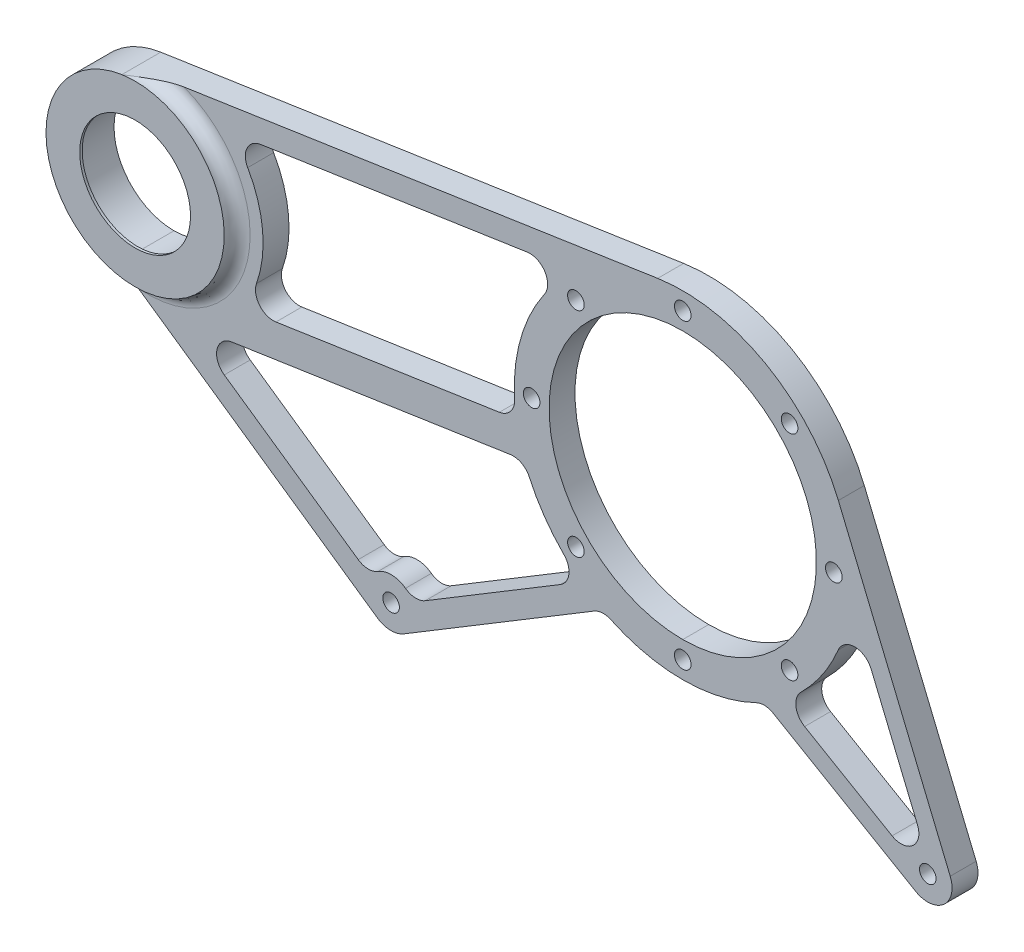
SolidWorks part; units mm, degrees
material "6061-T6 (SS)"
ref_plane "Front Plane" through (0, 0, 0) normal (0, 0, 1) x (1, 0, 0)
ref_plane "Top Plane" through (0, 0, 0) normal (0, 1, 0) x (1, 0, 0)
ref_plane "Right Plane" through (0, 0, 0) normal (1, 0, 0) x (0, 0, -1)
sketch "Sketch1" plane through (0, 0, 0) normal (0, 0, 1) x (1, 0, 0)
  line L0 (-329.0358, 136.1378) -> (-124.1059, 166.9079)
  line L1 (-343.7594, 72.9056) -> (-234.0298, -3.2296)
  line L2 (-223.6766, -3.5577) -> (-149.0272, 41.5159)
  line L3 (-114.3, 88.9) -> (-114.3, 101.6) construction
  line L4 (-53.3056, 126.9173) -> (-9.4675, 21.3025)
  line L5 (-23.0618, 9.4221) -> (-78.8665, 41.9532)
  circle A0 centre (-114.3, 88.9) radius 82.9716 construction
  circle A1 centre (-228.6, -20.8038) radius 12.7 construction
  circle A2 centre (0, 0) radius 12.7 construction
  circle A3 centre (-323.85, 101.6) radius 114 construction
  circle A4 centre (-323.85, 101.6) radius 23.5
  circle A5 centre (-114.3, 101.6) radius 52.3875
  arc A6 (-142.4404, 41.8555) -> (-85.4371, 42.2012) centre (-114.3, 101.6) ccw
  circle A7 centre (-323.85, 101.6) radius 34.925
  arc A8 (-223.6766, -3.5577) -> (-234.0298, -3.2296) centre (-228.6, 4.5962) cw
  arc A9 (-9.4675, 21.3025) -> (-23.0618, 9.4221) centre (-18.2648, 17.651) cw
  circle A10 centre (-228.6, 4.5962) radius 3.2512
  circle A11 centre (-18.2648, 17.651) radius 3.2512
  arc A12 (-142.4404, 41.8555) -> (-149.0272, 41.5159) centre (-145.4168, 35.5364) ccw
  arc A13 (-78.8665, 41.9532) -> (-85.4371, 42.2012) centre (-82.3843, 35.9187) ccw
  circle A14 centre (-114.3, 101.6) radius 66.04 construction
  arc A15 (-124.1059, 166.9079) -> (-53.3056, 126.9173) centre (-114.3, 101.6) cw
  dimension "D1" = 88.9
  dimension "D2" = 12.7
  dimension "D3" = 25.4
  dimension "D4" = 25.4
  dimension "D8" = 165.9433
  dimension "D9" = 228
  dimension "D10" = 47
  dimension "D12" = 104.775
  dimension "D14" = 132.08
  dimension "D15" = 69.85
  dimension "D16" = 9.525
  dimension "D18" = 9.525
  dimension "D20" = 6.5024
  dimension "D21" = 6.5024
  dimension "D23" = 6.985
  dimension "D24" = 6.985
  dimension "D25" = 66.04
  dimension "D5" = 228.6
  dimension "D6" = 20.8038
  dimension "D7" = 114.3
  dimension "D11" = 12.7
  dimension "D13" = 209.55
  dimension "D17" = 25.4
  dimension "D19" = 25.4
  dimension "D22" = 17.651
extrude "Boss-Extrude1" add sketch "Sketch1" along normal blind 10.16 contours A7 A4 | A8 L2 A6 L0 A7 L1 A10 | A6 A5 | A9 L4 A6 L5 A11 region at (-187.4243, 81.6254, 0) region at (-301.706, 127.3172, 0)
ref_point "Point2"
ref_point "Point4"
ref_plane "Plane2" through (-114.3, 0, 0) normal (1, 0, 0) x (0, 0, -1)
ref_plane "Plane3" through (-323.85, 0, 0) normal (1, 0, 0) x (0, 0, -1)
sketch "Sketch5" plane through (0, 0, 10.16) normal (0, 0, 1) x (1, 0, 0)
  circle A0 centre (-323.85, 101.6) radius 23.5
  circle A1 centre (-323.85, 101.6) radius 34.925
extrude "Boss-Extrude3" add sketch "Sketch5" along normal blind 5.08
fillet "Fillet2" radius 5.08 1 edges at (-289.835, 93.6796, 10.16)
sketch "Sketch6" plane through (0, 0, 15.24) normal (0, 0, 1) x (1, 0, 0)
  circle A0 centre (-323.85, 101.6) radius 23.5
  circle A1 centre (-323.85, 101.6) radius 21.722
  dimension "D1" = 47
  dimension "D2" = 1.778
extrude "Boss-Extrude4" add sketch "Sketch6" against normal blind 0.9677
split line "Split Line3"
split line "Split Line4"
sketch "Sketch7" plane through (0, 0, 0) normal (0, 0, 1) x (1, 0, 0)
  line L0 (-279.7929, 134.542) -> (-175.2648, 150.2368)
  line L1 (-300.8405, 140.3714) -> (-125.2445, 166.737)
  line L2 (-309.742, 139.0348) -> (-124.1059, 166.9079) construction
  line L3 (-327.7299, 61.7836) -> (-234.0298, -3.2296) construction
  line L4 (-327.7299, 61.7836) -> (-320.3344, 56.6523) construction
  line L5 (-293.9898, 49.1936) -> (-241.4832, 12.7622)
  line L6 (-215.2255, 11.93) -> (-162.2555, 43.9136)
  line L7 (-223.6766, -3.5577) -> (-149.0272, 41.5159) construction
  line L8 (-223.6766, -3.5577) -> (-149.0272, 41.5159) construction
  line L9 (-291.0451, 61.84) -> (-181.7958, 78.2437)
  line L10 (-273.7403, 77.2807) -> (-186.1633, 90.4303)
  line L11 (-32.2583, 23.6034) -> (-66.5305, 43.5822)
  line L12 (-22.2892, 32.3156) -> (-40.471, 76.1193)
  line L13 (-23.0618, 9.4221) -> (-78.8665, 41.9532) construction
  line L14 (-53.3056, 126.9173) -> (-9.4675, 21.3025) construction
  line L15 (-23.0618, 9.4221) -> (-78.8665, 41.9532) construction
  line L16 (-53.3056, 126.9173) -> (-9.4675, 21.3025) construction
  line L17 (-309.742, 139.0348) -> (-124.1059, 166.9079) construction
  circle A0 centre (-114.3, 101.6) radius 62.0284 construction
  circle A1 centre (-323.85, 101.6) radius 38.735 construction
  circle A2 centre (-323.85, 101.6) radius 45.085 construction
  arc A4 (-291.0451, 61.84) -> (-293.9898, 49.1936) centre (-290.0079, 54.9325) ccw
  arc A5 (-174.4017, 74.231) -> (-160.9335, 54.839) centre (-114.3, 101.6) ccw
  arc A6 (-160.9335, 54.839) -> (-162.2555, 43.9136) centre (-165.8659, 49.8931) cw
  arc A7 (-181.7958, 78.2437) -> (-174.4017, 74.231) centre (-180.7586, 71.3362) cw
  arc A8 (-284.805, 124.142) -> (-281.3603, 86.524) centre (-323.85, 101.6) cw
  arc A9 (-168.4954, 139.3377) -> (-180.2274, 97.7456) centre (-114.3, 101.6) ccw
  arc A10 (-180.2274, 97.7456) -> (-186.1633, 90.4303) centre (-187.2005, 97.3379) cw
  arc A11 (-284.805, 124.142) -> (-279.7929, 134.542) centre (-278.7557, 127.6344) cw
  arc A12 (-281.3603, 86.524) -> (-273.7403, 77.2807) centre (-274.7774, 84.1883) ccw
  arc A13 (-175.2648, 150.2368) -> (-168.4954, 139.3377) centre (-174.2276, 143.3292) cw
  arc A14 (-222.9669, 12.2769) -> (-233.7354, 12.6182) centre (-228.6, 4.5962) ccw
  arc A15 (-223.6766, -3.5577) -> (-223.0453, -3.1415) centre (-228.6, 4.5962) ccw
  arc A16 (-233.7354, 12.6182) -> (-241.4832, 12.7622) centre (-237.5013, 18.5011) cw
  arc A17 (-215.2255, 11.93) -> (-222.9669, 12.2769) centre (-218.836, 17.9095) cw
  arc A19 (-22.2892, 32.3156) -> (-32.2583, 23.6034) centre (-28.7405, 29.6379) cw
  arc A20 (-67.9184, 54.589) -> (-53.3671, 76.135) centre (-114.3, 101.6) ccw
  arc A21 (-40.471, 76.1193) -> (-53.3671, 76.135) centre (-46.9223, 73.4415) ccw
  arc A22 (-66.5305, 43.5822) -> (-67.9184, 54.589) centre (-63.0127, 49.6167) cw
  circle A23 centre (-114.3, 101.6) radius 66.04 construction
  point P31 (-308.45, 59.2267)
  point P33 (-172.4396, 79.9826)
  point P41 (-291.3157, 132.8118)
  point P45 (-154.09, 149.1844)
  point P64 (-78.8001, 50.7347)
  dimension "D1" = 6.35
  dimension "D3" = 8.89
  dimension "D5" = 90.17
  dimension "D6" = 124.0568
  dimension "D7" = 6.985
  dimension "D8" = 6.985
  dimension "D10" = 6.985
  dimension "D11" = 9.525
  dimension "D12" = 6.985
  dimension "D13" = 6.985
  dimension "D16" = 6.985
  dimension "D17" = 132.08
  dimension "D2" = 8.89
  dimension "D4" = 8.89
  dimension "D9" = 12.7
  dimension "D14" = 7.62
  dimension "D15" = 7.62
extrude "Cut-Extrude2" cut sketch "Sketch7" against normal through all both and the other way through all contours A17 L6 A6 A5 A7 L9 A4 L5 A16 A14 | A13 L0 A11 A8 A12 L10 A10 A9 | A22 L11 A19 L12 A21 A20 | A21 A20 A22 L11 A19 L12 region at (-228.3297, 114.1645, 0) region at (-224.0506, 46.8096, 0) region at (-44.9997, 50.0307, 0)
sketch "Sketch8" plane through (0, 0, 10.16) normal (0, 0, 1) x (1, 0, 0)
  line L0 (-114.3, 101.6) -> (-114.3, 160.8137) construction
  circle A0 centre (-114.3, 101.6) radius 59.2137 construction
  circle A1 centre (-114.3, 160.8137) radius 3.2512
  circle A2 centre (-72.4296, 143.4704) radius 3.2512
  circle A3 centre (-55.0862, 101.6) radius 3.2512
  circle A4 centre (-72.4296, 59.7296) radius 3.2512
  circle A5 centre (-114.3, 42.3863) radius 3.2512
  circle A6 centre (-156.1704, 59.7296) radius 3.2512
  circle A7 centre (-173.5137, 101.6) radius 3.2512
  circle A8 centre (-156.1704, 143.4704) radius 3.2512
  point P22 (-114.3, 101.6)
  dimension "D1" = 118.4275
  dimension "D2" = 6.5024
  dimension "D3" = 8
extrude "Cut-Extrude3" cut sketch "Sketch8" against normal through all both and the other way through all
